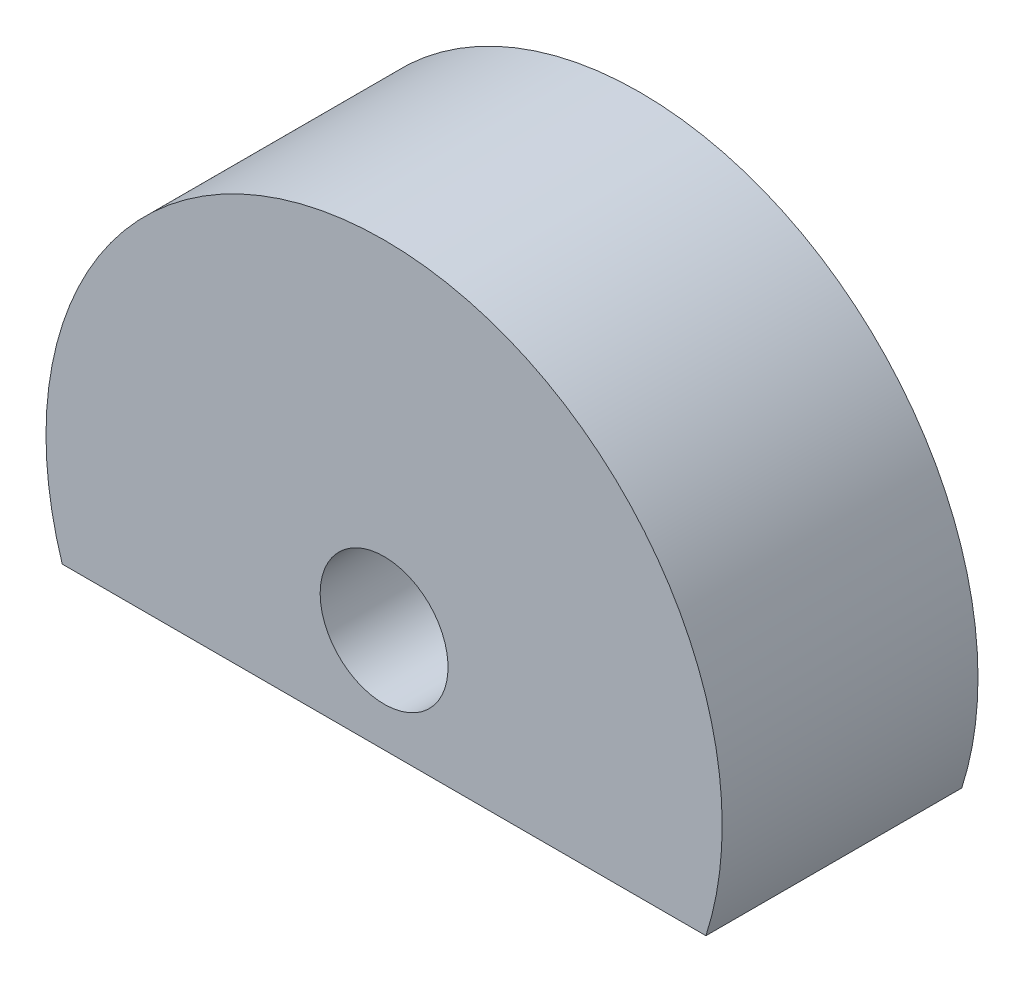
SolidWorks part; units mm, degrees
ref_plane "Front Plane" through (0, 0, 0) normal (0, 0, 1) x (1, 0, 0)
ref_plane "Top Plane" through (0, 0, 0) normal (0, 1, 0) x (1, 0, 0)
ref_plane "Right Plane" through (0, 0, 0) normal (1, 0, 0) x (0, 0, -1)
sketch "Sketch1" plane through (0, 0, 0) normal (0, 0, 1) x (1, 0, 0)
  circle A1 centre (-72.6, -136.95) radius 2.667
  dimension "D1" = 5.334
extrude "Boss-Extrude1" add sketch "Sketch1" along normal blind 6.35 and the other way blind 6.35 contours A1
sketch "Sketch2" plane through (0, 0, 6.35) normal (0, 0, 1) x (1, 0, 0)
  line L0 (-273.05, -152.4) -> (-12.7, -152.4) construction
  circle A0 centre (-72.6, -142.3293) radius 10.0707
  circle A2 centre (-72.6, -142.3293) radius 1.905
  point P2 (-72.6, -136.95)
  point P7 (-43.6, -139.7)
  dimension "D1" = 20.1414
  dimension "D2" = 3.81
extrude "Boss-Extrude2" add sketch "Sketch2" along normal up to surface (16 mm away)
sketch "Sketch4" plane through (0, 0, 22.35) normal (0, 0, -1) x (-1, 0, 0)
  line L1 (63.0137, -152.4) -> (82.1863, -152.4)
  line L2 (63.0137, -152.4) -> (63.0137, -145.415)
  line L3 (63.0137, -145.415) -> (82.1863, -145.415)
  line L4 (82.1863, -152.4) -> (82.1863, -145.415)
  line L5 (63.0137, -152.4) -> (82.1863, -145.415) construction
  line L6 (63.0137, -145.415) -> (82.1863, -152.4) construction
  circle A0 centre (72.6, -142.3293) radius 10.0707 construction
  point P4 (72.6, -148.9075)
  dimension "D1" = 6.985
extrude "Cut-Extrude2" cut sketch "Sketch4" along normal blind 7.62 contours L1 L4 L3 L2
sketch "Sketch6" plane through (0, -139.617, 0) normal (0, -1, 0) x (1, 0, 0)
  line L0 (-63.0137, 14.73) -> (-82.1863, 14.73) construction
  line L1 (-82.6707, 14.73) -> (-62.5293, 14.73)
  line L2 (-82.6707, 14.73) -> (-82.6707, -6.35)
  line L3 (-82.6707, -6.35) -> (-62.5293, -6.35)
  line L4 (-62.5293, 14.73) -> (-62.5293, -6.35)
  line L5 (-82.6707, 14.73) -> (-62.5293, -6.35) construction
  line L6 (-82.6707, -6.35) -> (-62.5293, 14.73) construction
  line L7 (-75.267, -6.35) -> (-69.933, -6.35) construction
  point P4 (-72.6, 4.19)
  point P9 (0, 0)
extrude "Cut-Extrude3" cut sketch "Sketch6" against normal through all both and the other way through all
